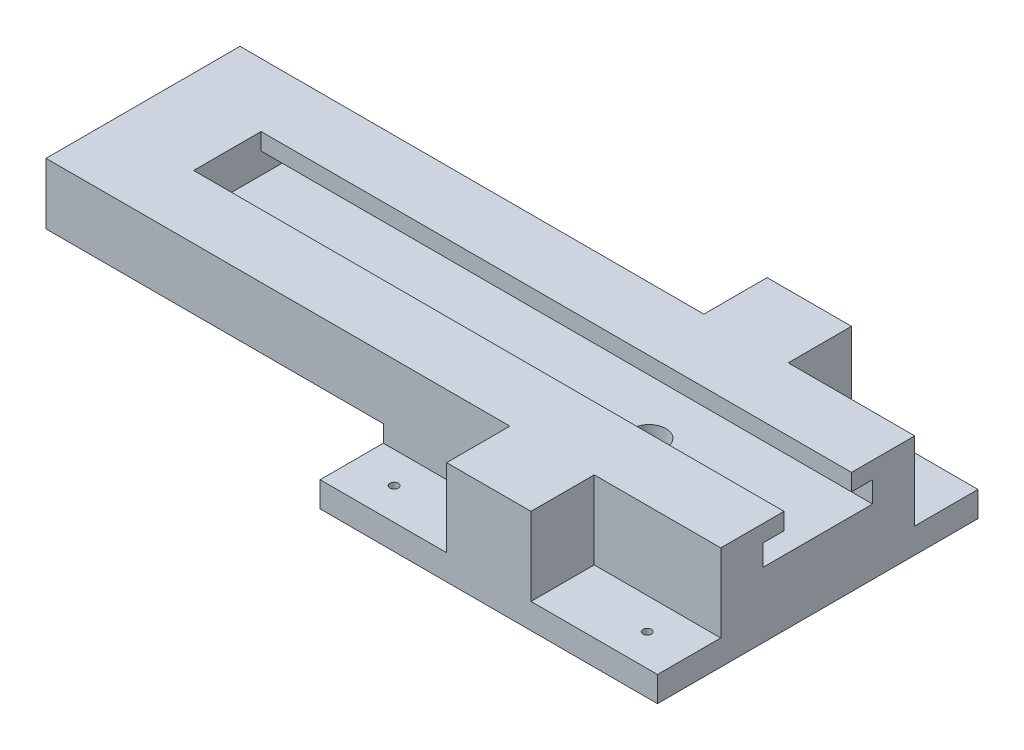
SolidWorks part; units mm, degrees
ref_plane "Front Plane" through (0, 0, 0) normal (0, 0, 1) x (1, 0, 0)
ref_plane "Top Plane" through (0, 0, 0) normal (0, 1, 0) x (1, 0, 0)
ref_plane "Right Plane" through (0, 0, 0) normal (1, 0, 0) x (0, 0, -1)
sketch "Sketch1" plane through (0, 0, 0) normal (0, 1, 0) x (1, 0, 0)
  line L2 (80, -16) -> (220, -16)
  line L3 (220, -16) -> (220, -46)
  line L4 (220, -46) -> (60, -46)
  line L7 (220, 30) -> (220, 0)
  line L8 (80, -16) -> (80, 0)
  line L9 (80, 0) -> (220, 0)
  line L10 (220, 30) -> (60, 30)
  line L11 (60, 30) -> (60, -46)
  dimension "D1" = 16
  dimension "D3" = 30
  dimension "D4" = 160
  dimension "D5" = 140
  dimension "D6" = 160
extrude "Boss-Extrude1" add sketch "Sketch1" along normal blind 4
sketch "Sketch2" plane through (0, 0, 0) normal (0, 1, 0) x (1, 0, 0)
  line L0 (209.7303, -8) -> (-59.5425, -8) construction
  line L1 (220, -8) -> (220, 5) construction
  line L4 (220, 5) -> (220, 30)
  line L5 (220, 30) -> (60, 30)
  line L6 (60, 30) -> (60, -46)
  line L7 (60, 30) -> (60, -46) construction
  line L8 (220, -21) -> (220, -46)
  line L10 (220, -46) -> (60, -46)
  line L11 (220, 5) -> (80, 5)
  line L12 (80, 5) -> (80, -21)
  line L13 (80, -21) -> (220, -21)
  point P18 (0, -8)
  point P19 (60, -8)
  dimension "D1" = 13
extrude "Boss-Extrude2" add sketch "Sketch2" against normal blind 5
sketch "Sketch3" plane through (0, 0, 0) normal (0, 1, 0) x (1, 0, 0)
  line L0 (60, 30) -> (220, 30)
  line L1 (220, 30) -> (220, -46)
  line L2 (220, -46) -> (60, -46)
  line L3 (60, -46) -> (60, 30)
extrude "Boss-Extrude3" add sketch "Sketch3" against normal blind 5.5 from offset 5 offset against normal yes
sketch "Sketch4" plane through (0, 0, 0) normal (0, 1, 0) x (1, 0, 0)
  line L0 (220, 30) -> (220, -46)
  line L1 (220, -46) -> (140, -46)
  line L2 (60, -46) -> (220, -46) construction
  line L3 (140, -46) -> (140, 30)
  line L4 (220, 30) -> (60, 30) construction
  line L5 (140, 30) -> (220, 30)
  dimension "D1" = 80
extrude "Boss-Extrude4" add sketch "Sketch4" against normal blind 10 from offset 10.5 contours L5 L0 L1 L3 offset against normal yes
sketch "Sketch17" plane through (0, 0, 0) normal (0, 1, 0) x (1, 0, 0)
  line L0 (220, -8) -> (180, -8) construction
  line L2 (220, 30) -> (220, -46) construction
  circle A1 centre (180, -8) radius 19
  dimension "D2" = 38
  dimension "D1" = 40
extrude "Boss-Extrude7" add sketch "Sketch17" against normal blind 8 from offset 20.5 offset against normal yes
sketch "Sketch5" plane through (0, 0, 0) normal (0, 1, 0) x (1, 0, 0)
  line L0 (180, -46) -> (180, 30) construction
  line L1 (220, -46) -> (140, -46) construction
  line L2 (140, 30) -> (220, 30) construction
  line L3 (220, -8) -> (140, -8) construction
  line L4 (220, 30) -> (220, -46) construction
  line L5 (140, -46) -> (140, 30) construction
  circle A0 centre (180, -8) radius 10.5
  dimension "D1" = 21
extrude "Cut-Extrude1" cut sketch "Sketch5" against normal blind 12 from offset 25 offset against normal yes
sketch "Sketch7" plane through (0, 0, 0) normal (0, 1, 0) x (1, 0, 0)
  circle A0 centre (180, -8) radius 1.5
  dimension "D1" = 3
extrude "Cut-Extrude2" cut sketch "Sketch7" against normal blind 25 from offset 4 offset against normal yes
sketch "Sketch8" plane through (0, 0, 0) normal (0, 1, 0) x (1, 0, 0)
  circle A0 centre (180, -8) radius 4
  dimension "D1" = 8
extrude "Cut-Extrude3" cut sketch "Sketch8" against normal blind 18.5 from offset 5 offset against normal yes
sketch "Sketch18" plane through (0, 0, 0) normal (0, 1, 0) x (1, 0, 0)
  line L0 (60, 30) -> (170, 30)
  line L1 (60, 30) -> (220, 30) construction
  line L2 (170, 30) -> (170, 15)
  line L3 (170, 15) -> (60, 15)
  line L4 (60, -46) -> (60, 30) construction
  line L5 (60, 15) -> (60, 30)
  line L6 (60, -8) -> (220, -8) construction
  line L8 (170, -46) -> (170, -31)
  line L9 (60, -46) -> (170, -46)
  line L10 (60, -31) -> (60, -46)
  line L11 (170, -31) -> (60, -31)
  line L12 (220, 30) -> (220, 15)
  line L13 (220, 30) -> (220, -46) construction
  line L14 (220, 15) -> (190, 15)
  line L15 (190, 15) -> (190, 30)
  line L16 (190, 30) -> (220, 30)
  line L17 (220, -46) -> (220, -31)
  line L18 (220, -31) -> (190, -31)
  line L19 (190, -46) -> (220, -46)
  line L20 (190, -31) -> (190, -46)
  dimension "D1" = 110
  dimension "D2" = 15
  dimension "D3" = 30
  dimension "D4" = 15
extrude "Cut-Extrude5" cut sketch "Sketch18" against normal blind 18.5 from offset 4
sketch "Sketch9" plane through (0, 0, 0) normal (0, 1, 0) x (1, 0, 0)
  line L0 (180, -8) -> (217.5, -8) construction
  line L1 (217.5, -8) -> (217.5, 29.5) construction
  line L2 (180, -8) -> (142.5, -8) construction
  line L3 (217.5, -8) -> (217.5, -45.5) construction
  line L4 (217.5, 29.5) -> (142.5, 30) construction
  line L5 (60, 30) -> (220, 30) construction
  line L6 (142.5, 30) -> (142.5, -45.5) construction
  line L7 (142.5, -45.5) -> (217.5, -45.5) construction
  line L8 (180, 29.75) -> (180, -45.5) construction
  line L9 (142.5, 22.45) -> (150, 22.45) construction
  line L10 (150, 22.45) -> (150, 29.95) construction
  line L11 (150, -38.45) -> (150, -45.95) construction
  line L12 (142.5, -38.45) -> (150, -38.45) construction
  line L13 (210, 22.45) -> (210, 29.95) construction
  line L14 (217.5, 22.45) -> (210, 22.45) construction
  line L15 (210, -38.45) -> (210, -45.95) construction
  line L16 (217.5, -38.45) -> (210, -38.45) construction
  circle A1 centre (180, -8) radius 30 construction
  circle A2 centre (150, 22.45) radius 1
  circle A3 centre (150, -38.45) radius 1
  circle A4 centre (210, 22.45) radius 1
  circle A5 centre (210, -38.45) radius 1
  dimension "D1" = 37.5
  dimension "D2" = 60
  dimension "D8" = 2
  dimension "D3" = 7.5
  dimension "D4" = 37.5
  dimension "D5" = 37.5
  dimension "D6" = 7.5
  dimension "D7" = 37.5
extrude "Cut-Extrude6" cut sketch "Sketch9" against normal blind 40 from offset 4
